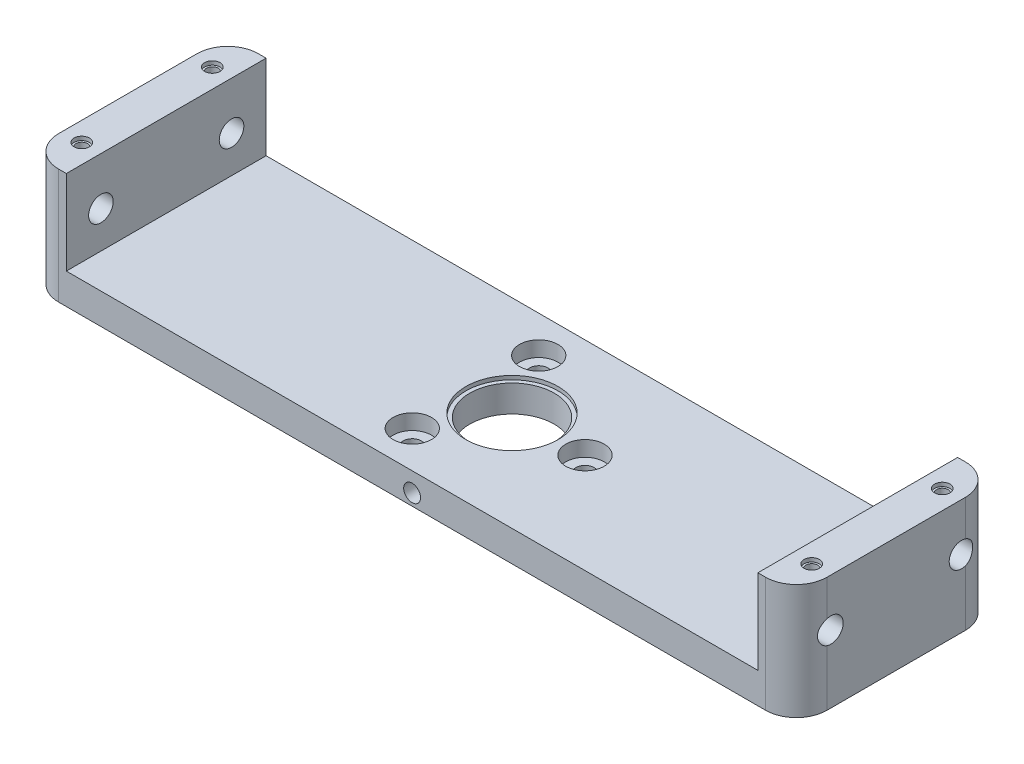
SolidWorks part; units mm, degrees
ref_plane "前视基准面" through (0, 0, 0) normal (0, 0, 1) x (1, 0, 0)
ref_plane "上视基准面" through (0, 0, 0) normal (0, 1, 0) x (1, 0, 0)
ref_plane "右视基准面" through (0, 0, 0) normal (1, 0, 0) x (0, 0, -1)
other "Configuration Table"
sketch "草图1" plane through (0, 0, 0) normal (0, 1, 0) x (1, 0, 0)
  line L1 (-50, 13) -> (50, 13)
  line L2 (-50, 13) -> (-50, -13)
  line L3 (-50, -13) -> (50, -13)
  line L4 (50, 13) -> (50, -13)
  line L5 (-50, 13) -> (50, -13) construction
  line L6 (-50, -13) -> (50, 13) construction
  point P0 (0, 0)
  dimension "D1" = 100
  dimension "D2" = 26
extrude "凸台-拉伸1" add sketch "草图1" along normal blind 15
sketch "草图2" plane through (0, 15, 0) normal (0, 1, 0) x (1, 0, 0)
  line L0 (0, 34.9924) -> (0, -36.2384) construction
  line L1 (-45, 13) -> (-45, -13)
  line L2 (45, 13) -> (45, -13)
  line L3 (-50, -13) -> (50, -13) construction
  line L4 (50, 13) -> (-50, 13) construction
  line L5 (-45, -13) -> (45, -13)
  line L6 (45, 13) -> (-45, 13)
  line L8 (-45, 34.9924) -> (-45, -36.2384) construction
  line L9 (45, 34.9924) -> (45, -36.2384) construction
  dimension "D1" = 45
  dimension "D2" = 45
extrude "切除-拉伸1" cut sketch "草图2" against normal blind 11
sketch "草图3" plane through (50, 0, 0) normal (1, 0, 0) x (0, 0, -1)
  line L0 (0, -4.0303) -> (0, 26.6544) construction
  line L1 (8.5, -4.0303) -> (8.5, 26.6544) construction
  line L2 (-8.5, -4.0303) -> (-8.5, 26.6544) construction
  line L7 (-13, 8.8) -> (13, 8.8)
  line L8 (-13, 8.8) -> (13, 8.8) construction
  point P15 (-8.5, 8.8)
  point P17 (8.5, 8.8)
  dimension "D1" = 8.5
  dimension "D2" = 8.5
  dimension "D4" = 8.8
sketch "草图5" plane through (0, 4, 0) normal (0, 1, 0) x (1, 0, 0)
  circle A0 centre (0, 0) radius 5.5
  dimension "D1" = 11
extrude "切除-拉伸2" cut sketch "草图5" against normal through all
sketch "草图6" plane through (0, 4, 0) normal (0, 1, 0) x (1, 0, 0)
  circle A0 centre (0, 0) radius 6
  dimension "D1" = 12
extrude "切除-拉伸3" cut sketch "草图6" against normal blind 0.5
sketch "草图7" plane through (0, 4, 0) normal (0, 1, 0) x (1, 0, 0)
  line L0 (-53.1635, 0) -> (64.5854, 0) construction
  line L1 (0, 28.6585) -> (0, -25.0242) construction
  line L2 (9.5, 28.6585) -> (9.5, -25.0242) construction
  point P7 (9.5, 0)
  dimension "D1" = 9.5
hole_wizard "M2 六角头螺栓的柱形沉头孔1" positions "草图7" profile "草图8" counterbore size "M2" standard "GB" end condition up to next
sketch "草图8" plane through (9.5, 4, 0) normal (1, 0, 0) x (0, 0, 1)
  line L0 (0, 0) -> (0, 4)
  line L1 (0, 4) -> (1.2, 4)
  line L3 (1.2, 4) -> (1.2, 2)
  line L4 (1.2, 2) -> (2.5, 2)
  line L5 (2.5, 2) -> (2.5, 0)
  line L7 (2.5, 0) -> (0, 0)
  line L11 (0, -6.35) -> (0, 107.95) construction
  dimension "通孔孔直径" = 2.4
  dimension "通孔孔深度" = 4
  dimension "柱形沉头孔直径" = 5
  dimension "柱形沉头孔深度" = 2
pattern_circular "阵列(圆周)1" count 3 every 120 about axis through (0, 3.5, 0) along (0, 1, 0) of "M2 六角头螺栓的柱形沉头孔1"
hole_wizard "Ø3.2 (3.2) 直径孔1" positions "草图3" profile "草图4" hole size "Ø3.2" standard "GB" end condition through all
sketch "草图4" plane through (50, 8.8, -8.5) normal (0, 1, 0) x (0, 0, -1)
  line L0 (0, 0) -> (0, 100)
  line L1 (0, 100) -> (1.6, 100)
  line L2 (1.6, 100) -> (1.6, 0)
  line L5 (1.6, 0) -> (0, 0)
  line L11 (0, -6.35) -> (0, 107.95) construction
  dimension "通孔孔直径" = 3.2
  dimension "通孔孔深度" = 100
sketch "草图11" plane through (0, 15, 0) normal (0, 1, 0) x (1, 0, 0)
  line L0 (-67.3889, 0) -> (66.1429, 0) construction
  line L1 (-67.3889, -8.5) -> (66.1429, -8.5) construction
  line L6 (0, 20.2835) -> (0, -24.0339) construction
  line L7 (-47.5, 13) -> (-47.5, -13)
  line L8 (-47.5, 13) -> (-47.5, -13) construction
  circle A0 centre (-47.5, -8.5) radius 1.5
  point P5 (-47.5, -8.5)
  dimension "D3" = 3
  dimension "D1" = 8.5
  dimension "D2" = 2.5
sketch "草图9" plane through (0, 0, 13) normal (0, 0, 1) x (1, 0, 0)
  line L0 (0, 31.4666) -> (0, -16.0899) construction
  line L3 (-45, 1.5) -> (45, 1.5)
  line L4 (-45, 1.5) -> (45, 1.5) construction
  circle A0 centre (0, 1.5) radius 1.1
  dimension "D2" = 2.2
  dimension "D1" = 2.5
extrude "切除-拉伸4" cut sketch "草图9" against normal blind 10
sketch "草图12" plane through (0, 0, -13) normal (0, 0, -1) x (-1, 0, 0)
  line L0 (0, 31.709) -> (0, -21.6622) construction
  line L1 (-45, 4) -> (45, 4) construction
  line L2 (-1, 7) -> (1, 7)
  line L3 (-1, 7) -> (-1, 1)
  line L4 (-1, 1) -> (1, 1)
  line L5 (1, 7) -> (1, 1)
  line L6 (-1, 7) -> (1, 1) construction
  line L7 (-1, 1) -> (1, 7) construction
  point P3 (0, 4)
  dimension "D1" = 6
  dimension "D2" = 2
extrude "切除-拉伸6" [suppressed] cut sketch "草图12" against normal blind 10
fillet "圆角1" radius 4 4 edges at (50, 7.5, -13) (50, 7.5, 13) (-50, 7.5, 13) (-50, 7.5, -13)
hole_wizard "M1.6 六角头螺栓的柱形沉头孔1" positions "草图11" profile "草图13" counterbore size "M1.6" standard "GB" end condition up to next
sketch "草图13" plane through (-47.5, 15, 8.5) normal (1, 0, 0) x (0, 0, 1)
  line L0 (0, 0) -> (0, 4.6)
  line L1 (0, 4.6) -> (0.75, 4.6)
  line L3 (0.75, 4.6) -> (0.75, 0.5)
  line L4 (0.75, 0.5) -> (1, 0.5)
  line L5 (1, 0.5) -> (1, 0)
  line L7 (1, 0) -> (0, 0)
  line L11 (0, -6.35) -> (0, 107.95) construction
  dimension "通孔孔直径" = 1.5
  dimension "通孔孔深度" = 4.6
  dimension "柱形沉头孔直径" = 2
  dimension "柱形沉头孔深度" = 0.5
mirror "镜向1" about plane through (0, 0, 0) normal (1, 0, 0) of "M1.6 六角头螺栓的柱形沉头孔1" second plane through (0, 0, 0) second plane normal (0, 0, 1)
